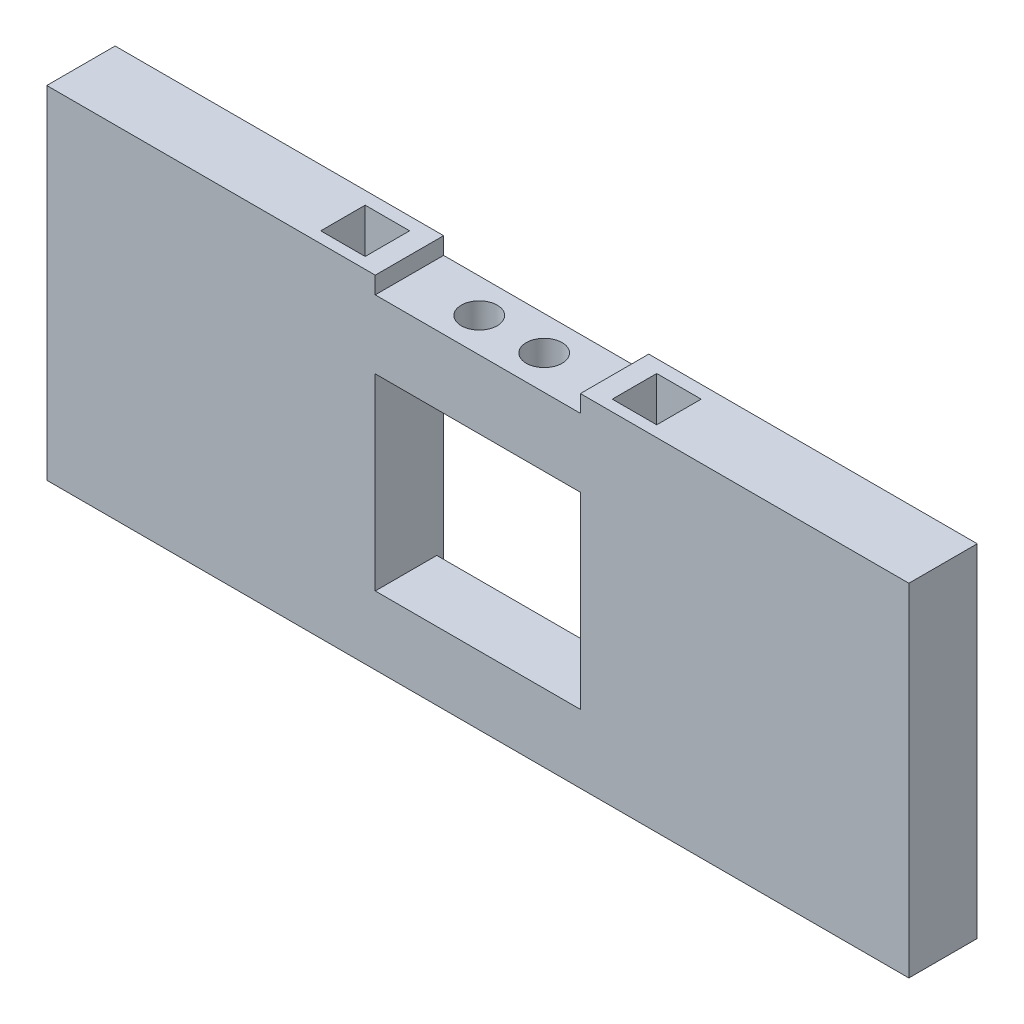
SolidWorks part; units mm, degrees
ref_plane "Front Plane" through (0, 0, 0) normal (0, 0, 1) x (1, 0, 0)
ref_plane "Top Plane" through (0, 0, 0) normal (0, 1, 0) x (1, 0, 0)
ref_plane "Right Plane" through (0, 0, 0) normal (1, 0, 0) x (0, 0, -1)
sketch "Sketch1" plane through (0, 0, 0) normal (0, 0, 1) x (1, 0, 0)
  line L1 (-107.8214, 92.0904) -> (-7.8214, 92.0904)
  line L3 (-107.8214, 44.0904) -> (-7.8214, 44.0904)
  line L5 (-107.8214, 92.0904) -> (-182.8214, 92.0904)
  line L7 (-107.8214, 44.0904) -> (-182.8214, 44.0904)
  line L8 (-182.8214, 92.0904) -> (-182.8214, 44.0904)
  line L9 (-7.8214, 92.0904) -> (117.1786, 92.0904)
  line L11 (-7.8214, 44.0904) -> (117.1786, 44.0904)
  line L12 (117.1786, 92.0904) -> (117.1786, 44.0904)
  dimension "D1" = 48
  dimension "D2" = 100
  dimension "D3" = 75
  dimension "D4" = 125
extrude "Boss-Extrude1" add sketch "Sketch1" along normal blind 20
sketch "Sketch5" plane through (0, 92.0904, 0) normal (0, 1, 0) x (1, 0, 0)
  line L0 (-182.8214, -20) -> (-157.8214, -20) construction
  line L2 (117.1786, -20) -> (-182.8214, -20) construction
  line L3 (-157.8214, -20) -> (-57.8214, -20) construction
  line L4 (-57.8214, -20) -> (-66.3214, -20) construction
  line L5 (-66.3214, -20) -> (-66.3214, -16) construction
  line L6 (-66.3214, -16) -> (-66.3214, -10) construction
  line L7 (-66.3214, -10) -> (-47.3214, -10) construction
  circle A0 centre (-66.3214, -10) radius 5.25
  circle A1 centre (-47.3214, -10) radius 5.25
extrude "Cut-Extrude4" cut sketch "Sketch5" against normal blind 20
sketch "Sketch6" plane through (0, 92.0904, 0) normal (0, 1, 0) x (1, 0, 0)
  line L0 (-182.8214, 0) -> (-105.6914, 0) construction
  line L1 (117.1786, 0) -> (-182.8214, 0) construction
  line L2 (-105.6914, 0) -> (-105.6914, -4) construction
  line L3 (-105.9414, -3.75) -> (-92.9414, -3.75)
  line L8 (-92.9414, -3.75) -> (-92.9414, -16.75)
  line L9 (-105.9414, -16.75) -> (-92.9414, -16.75)
  line L10 (-105.9414, -3.75) -> (-105.9414, -16.75)
extrude "Cut-Extrude5" cut sketch "Sketch6" against normal blind 15.5
sketch "Sketch7" plane through (0, 92.0904, 0) normal (0, 1, 0) x (1, 0, 0)
  line L0 (117.1786, 0) -> (-7.9138, 0) construction
  line L1 (117.1786, 0) -> (-182.8214, 0) construction
  line L2 (-7.9138, 0) -> (-7.9138, -4) construction
  line L3 (-7.6638, -3.75) -> (-20.6638, -3.75)
  line L8 (-20.6638, -3.75) -> (-20.6638, -16.75)
  line L9 (-7.6638, -16.75) -> (-20.6638, -16.75)
  line L10 (-7.6638, -3.75) -> (-7.6638, -16.75)
extrude "Cut-Extrude6" cut sketch "Sketch7" against normal blind 15.5
sketch "Sketch8" plane through (0, 0, 20) normal (0, 0, 1) x (1, 0, 0)
  line L0 (117.1786, 44.0904) -> (117.1786, 92.0904) construction
  line L1 (-182.8214, 44.0904) -> (117.1786, 44.0904)
  line L2 (-182.8214, 44.0904) -> (-182.8214, -57.9096)
  line L3 (-182.8214, -57.9096) -> (117.1786, -57.9096)
  line L4 (117.1786, 44.0904) -> (117.1786, -57.9096)
  dimension "D1" = 150
extrude "Boss-Extrude2" add sketch "Sketch8" against normal up to surface (20 mm away) up to face at (-32.8214, 68.0904, 0)
sketch "Sketch9" plane through (0, 92.0904, 0) normal (0, 1, 0) x (1, 0, 0)
  line L1 (-105.9414, -3.75) -> (-105.9414, -16.75) construction
  line L2 (-7.6638, -3.75) -> (-7.6638, -16.75) construction
  line L4 (117.1786, 0) -> (-182.8214, 0) construction
  line L5 (69.3362, 0) -> (69.3362, -20) construction
  line L6 (117.1786, -20) -> (-182.8214, -20) construction
  line L8 (117.1786, -20) -> (69.3362, -20)
  line L9 (117.1786, -20) -> (117.1786, 0)
  line L10 (117.1786, 0) -> (69.3362, 0)
  line L11 (69.3362, -20) -> (69.3362, 0)
  dimension "D1" = 77
extrude "Cut-Extrude7" cut sketch "Sketch9" against normal up to vertex (150 mm away) up to point (117.1786, -57.9096, 0)
sketch "Sketch11" plane through (0, 0, 20) normal (0, 0, 1) x (1, 0, 0)
  line L0 (69.3362, 92.0904) -> (-182.8214, 92.0904) construction
  line L1 (-56.7426, 92.0904) -> (-56.7426, 62.0904) construction
  line L3 (-26.7426, 62.0904) -> (-26.7426, 12.0904)
  line L4 (-26.7426, 12.0904) -> (-86.7426, 12.0904)
  line L5 (-86.7426, 12.0904) -> (-86.7426, 62.0904)
  line L8 (-26.7426, 62.0904) -> (-26.7426, 64.0904)
  line L9 (-26.7426, 64.0904) -> (-86.7426, 64.0904)
  line L10 (-86.7426, 62.0904) -> (-86.7426, 64.0904)
  point P5 (69.3362, 92.0904)
  point P10 (-56.7426, 62.0904)
  point P12 (-56.7426, 62.0904)
  dimension "D1" = 30
  dimension "D2" = 60
  dimension "D4" = 2
extrude "Cut-Extrude9" cut sketch "Sketch11" against normal blind 40
ref_plane "Plane1" through (-86.7426, 0, 0) normal (1, 0, 0) x (0, 0, -1)
sketch "Sketch14" plane through (-86.7426, 0, 0) normal (1, 0, 0) x (0, 0, -1)
  line L0 (0, 64.0904) -> (-20, 67.0904)
  line L3 (-20, -57.9096) -> (-20, 92.0904) construction
  line L4 (-20, 67.0904) -> (-20, 64.0904)
  line L9 (0, 64.0904) -> (-20, 64.0904)
extrude "Cut-Extrude10" cut sketch "Sketch14" along normal up to surface (60 mm away) up to face at (-26.7426, 38.0904, 10)
sketch "Sketch17" plane through (0, 0, 0) normal (0, 0, -1) x (-1, 0, 0)
  line L0 (-69.3362, 92.0904) -> (182.8214, 92.0904) construction
  line L1 (86.7426, 92.0904) -> (26.7426, 92.0904)
  line L2 (86.7426, 92.0904) -> (86.7426, 87.0904)
  line L3 (86.7426, 87.0904) -> (26.7426, 87.0904)
  line L4 (26.7426, 92.0904) -> (26.7426, 87.0904)
  line L5 (86.7426, 64.0904) -> (86.7426, 12.0904) construction
  line L6 (26.7426, 12.0904) -> (26.7426, 64.0904) construction
  dimension "D1" = 0
  dimension "D2" = 0
  dimension "D3" = 5
extrude "Cut-Extrude12" cut sketch "Sketch17" against normal blind 38
ref_plane "Plane2" through (-26.7426, 0, 0) normal (-1, 0, 0) x (0, 0, 1)
sketch "Sketch19" plane through (-26.7426, 0, 0) normal (-1, 0, 0) x (0, 0, 1)
  line L0 (0, 12.0904) -> (2, 12.0904)
  line L1 (0, 12.0904) -> (20, 12.0904) construction
  line L2 (0, -57.9096) -> (0, 92.0904) construction
  line L3 (2, 12.0904) -> (8, -57.9096)
  line L4 (0, -57.9096) -> (20, -57.9096) construction
  line L5 (8, -57.9096) -> (0, -57.9096)
  line L6 (0, -57.9096) -> (0, 12.0904)
  dimension "D1" = 8
extrude "Cut-Extrude13" cut sketch "Sketch19" along normal up to surface (60 mm away) up to face at (-86.7426, 38.8404, 10)
sketch "Sketch15" plane through (0, 92.0904, 0) normal (0, 1, 0) x (1, 0, 0)
  line L0 (-66.3214, -10) -> (-47.3214, -10) construction
  line L1 (69.3362, 0) -> (-26.7426, 0) construction
  line L2 (-76.8214, -20) -> (-36.8214, -20)
  line L3 (-76.8214, -20) -> (-76.8214, 0)
  line L4 (-76.8214, 0) -> (-36.8214, 0)
  line L5 (-36.8214, -20) -> (-36.8214, 0)
  line L6 (-76.8214, -20) -> (-36.8214, 0) construction
  line L7 (-76.8214, 0) -> (-36.8214, -20) construction
  circle A0 centre (-66.3214, -10) radius 5.25 construction
  circle A1 centre (-47.3214, -10) radius 5.25 construction
  circle A2 centre (-66.3214, -10) radius 5.25
  circle A3 centre (-47.3214, -10) radius 5.25
  point P7 (-56.8214, -10)
  dimension "D1" = 40
extrude "Cut-Extrude11" cut sketch "Sketch15" against normal blind 5 rebuild error yes
sketch "Sketch10" plane through (0, 0, 0) normal (0, 0, -1) x (-1, 0, 0)
  line L3 (-69.3362, -7.9096) -> (182.8214, -7.9096)
  line L6 (182.8214, 92.0904) -> (182.8214, -57.9096) construction
  line L8 (-69.3362, -57.9096) -> (182.8214, -57.9096)
  line L9 (-69.3362, -57.9096) -> (-69.3362, -7.9096)
  line L11 (182.8214, -57.9096) -> (182.8214, -7.9096)
  dimension "D1" = 50
extrude "Cut-Extrude8" cut sketch "Sketch10" against normal blind 310
